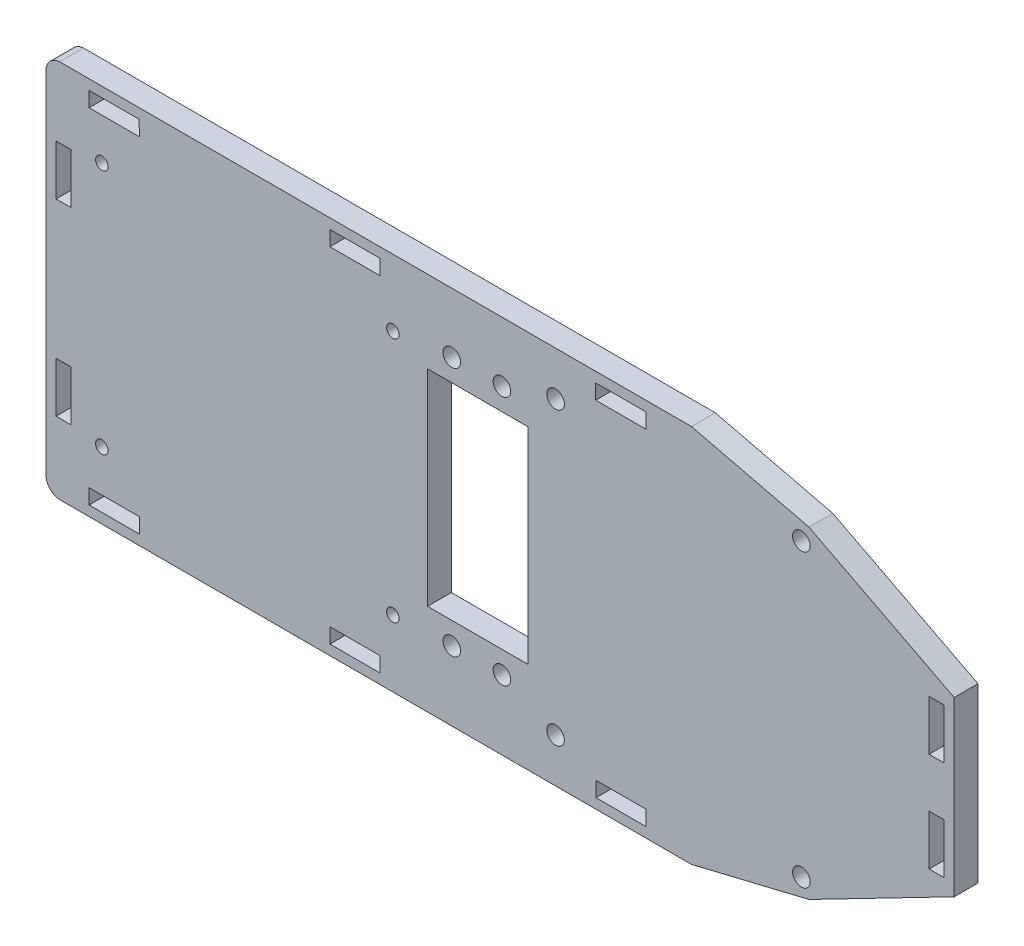
SolidWorks part; units mm, degrees
ref_plane "Front Plane" through (0, 0, 0) normal (0, 0, 1) x (1, 0, 0)
ref_plane "Top Plane" through (0, 0, 0) normal (0, 1, 0) x (1, 0, 0)
ref_plane "Right Plane" through (0, 0, 0) normal (1, 0, 0) x (0, 0, -1)
sketch "Sketch1" plane through (0, 0, 0) normal (0, 0, 1) x (1, 0, 0)
  line L1 (-90.5, -37.785) -> (90.5, -37.785)
  line L2 (-90.5, -37.785) -> (-90.5, 37.785)
  line L3 (-90.5, 37.785) -> (90.5, 37.785)
  line L4 (90.5, -37.785) -> (90.5, 37.785)
  line L5 (-90.5, -37.785) -> (90.5, 37.785) construction
  line L6 (-90.5, 37.785) -> (90.5, -37.785) construction
  point P0 (0, 0)
extrude "Boss-Extrude2" add sketch "Sketch1" along normal blind 4.75
sketch "Sketch6" plane through (0, 0, 4.75) normal (0, 0, 1) x (1, 0, 0)
  line L0 (-90.5, 0) -> (90.5, 0) construction
  line L1 (-90.5, 37.785) -> (-90.5, -37.785) construction
  line L2 (90.5, -37.785) -> (90.5, 37.785) construction
  line L3 (0, 37.785) -> (0, -37.785) construction
  line L4 (90.5, 37.785) -> (-90.5, 37.785) construction
  line L5 (-90.5, -37.785) -> (90.5, -37.785) construction
  line L6 (-90.5, 34.4318) -> (-90.5, -34.4318)
  line L7 (90.5, 17.2) -> (90.5, -17.2)
  line L10 (-21.3732, 40.787) -> (-21.3732, -34.783) construction
  line L11 (-81.9134, 32.786) -> (-71.8797, 32.7858)
  line L12 (-88.5, 23.75) -> (-85.5, 23.75)
  line L13 (-88.5, 23.75) -> (-88.5, 13.75)
  line L14 (-88.5, 13.75) -> (-85.5, 13.75)
  line L15 (-85.5, 23.75) -> (-85.5, 13.75)
  line L16 (-88.5, -13.75) -> (-85.5, -13.75)
  line L17 (-88.5, -13.75) -> (-88.5, -23.75)
  line L18 (-88.5, -23.75) -> (-85.5, -23.75)
  line L19 (-85.5, -13.75) -> (-85.5, -23.75)
  line L20 (-33.9297, 32.785) -> (-33.9309, 35.785)
  line L21 (-33.9297, 32.785) -> (-23.9273, 32.7887)
  line L22 (-33.9309, 35.785) -> (-23.931, 35.785)
  line L23 (-23.9273, 32.7887) -> (-23.931, 35.785)
  line L24 (-71.8797, 32.7858) -> (-71.9473, 35.785)
  line L25 (-81.9134, 32.786) -> (-81.9472, 35.785)
  line L26 (-81.9472, 35.785) -> (-71.9473, 35.785)
  line L27 (-81.9134, -32.785) -> (-71.8797, -32.7852)
  line L28 (-71.9135, -35.785) -> (-71.8797, -32.7852)
  line L29 (-81.9135, -35.785) -> (-71.9135, -35.785)
  line L30 (-81.9135, -35.785) -> (-81.9134, -32.785)
  line L31 (-33.9026, -35.7859) -> (-23.8868, -35.7861)
  line L32 (-33.9026, -35.7859) -> (-33.9037, -32.7859)
  line L33 (-23.8868, -35.7861) -> (-23.8868, -32.7861)
  line L34 (-33.9037, -32.7859) -> (-23.8868, -32.7861)
  line L35 (85.5, 14.9) -> (85.5, 4.9)
  line L36 (88.5, 14.9) -> (88.5, 4.9)
  line L37 (85.5, 4.9) -> (88.5, 4.9)
  line L38 (85.5, 14.9) -> (88.5, 14.9)
  line L40 (29.053, 32.7887) -> (29.053, 35.785)
  line L41 (19.053, 32.7887) -> (29.053, 32.7887)
  line L42 (19.053, 32.7887) -> (19.053, 35.785)
  line L43 (19.053, 35.785) -> (29.053, 35.785)
  line L44 (19.1132, -32.785) -> (29.053, -32.785)
  line L45 (19.1132, -35.785) -> (19.1132, -32.785)
  line L46 (19.1132, -35.785) -> (29.053, -35.785)
  line L47 (29.053, -35.785) -> (29.053, -32.785)
  line L50 (-87.3981, 37.785) -> (38.1419, 37.785)
  line L51 (-14.4594, 21.457) -> (5.5406, 21.457)
  line L52 (-14.4594, 21.457) -> (-14.4594, -19.543)
  line L53 (-14.4594, -19.543) -> (5.5406, -19.543)
  line L54 (5.5406, 21.457) -> (5.5406, -19.543)
  line L58 (-87.3981, -37.785) -> (38.1419, -37.785)
  line L60 (85.5, -14.9) -> (88.5, -14.9)
  line L61 (88.5, -14.9) -> (88.5, -4.9)
  line L62 (85.5, -4.9) -> (88.5, -4.9)
  line L63 (85.5, -14.9) -> (85.5, -4.9)
  line L64 (38.1419, -37.785) -> (61.5528, -32.1352)
  line L65 (61.5528, -32.1352) -> (90.5, -17.2)
  line L66 (38.1419, 37.785) -> (61.5528, 32.14)
  line L67 (61.5528, 32.14) -> (90.5, 17.2)
  arc A0 (-87.3981, 37.785) -> (-90.5, 34.4318) centre (-87.5923, 34.8533) ccw
  arc A1 (-90.5, -34.4318) -> (-87.3981, -37.785) centre (-87.5923, -34.8533) ccw
  circle A8 centre (-9.6294, 25.857) radius 1.75
  circle A9 centre (0.3706, 25.857) radius 1.75
  circle A10 centre (0.3706, -23.943) radius 1.75
  circle A11 centre (-9.6294, -23.943) radius 1.75
  circle A12 centre (11.053, -29) radius 1.75
  circle A13 centre (11.053, 29) radius 1.75
  circle A14 centre (60.053, -29) radius 1.75
  circle A15 centre (60.053, 29) radius 1.75
  circle A16 centre (-79.3732, 24.5) radius 1.25
  circle A17 centre (-79.3732, -24.5) radius 1.25
  circle A18 centre (-21.3732, -24.5) radius 1.25
  circle A19 centre (-21.3732, 24.5) radius 1.25
  point P18 (0, 0)
  point P21 (90.5, 0)
  point P22 (0, 0)
  line M4 (90.5, -37.785) -> (90.5, 37.785)
  line M5 (90.5, 37.785) -> (-90.5, 37.785)
  line M6 (-90.5, 37.785) -> (-90.5, -37.785)
  line M7 (-90.5, -37.785) -> (90.5, -37.785)
  dimension "D1" = 58
  dimension "D3" = 49
  dimension "D2" = 29
  dimension "D4" = 58
  dimension "D10" = 2
  dimension "D11" = 4.4
  dimension "D16" = 32.14
  dimension "D17" = 2
  dimension "D5" = 2
  dimension "D6" = 2
  dimension "D7" = 2
  dimension "D8" = 43
  dimension "D9" = 49.8
  dimension "D12" = 4.4
  dimension "D13" = 58
  dimension "D14" = 49
  dimension "D15" = 24.5
extrude "Cut-Extrude7" cut sketch "Sketch6" against normal blind 9 contours L38 L35 L37 L36 | L43 L42 L41 L40 | A9 | A8 | A11 | A10 | L46 L47 L44 L45 | L21 L23 L22 L20 | L26 L25 L11 L24 | A0 M5 M6 | L15 L12 L13 L14 | L19 L16 L17 L18 | A1 M6 M7 | L30 L29 L28 L27 | A16 | L34 L32 L31 L33 | L65 L64 M7 M4 | L66 L67 M4 M5 | L54 L51 L52 L53 | A17 | A18 | L44 L47 L46 L45 | A10 | L52 L51 L54 L53 | L60 L61 L62 L63 | A12 | A14 | A13 | A15 | A19 region at (-89.8524, 37.1595, 4.75) region at (-89.8524, -37.1595, 4.75) region at (75.0644, 31.3167, 4.75) region at (75.0611, -31.3164, 4.75) region at (-76.9218, 34.2846, 4.75) region at (-87, 18.75, 4.75) region at (-87, -18.75, 4.75) region at (-28.9307, 34.2859, 4.75) region at (-76.9051, -34.2842, 4.75) region at (-28.895, -34.286, 4.75) region at (87, 9.9, 4.75) region at (24.053, 34.2869, 4.75) region at (24.0831, -34.285, 4.75) region at (-4.4594, 0.957, 4.75) region at (-9.6294, 25.857, 4.75) region at (0.3706, 25.857, 4.75) region at (0.3706, -23.943, 4.75) region at (-9.6294, -23.943, 4.75) region at (-79.3732, 24.5, 4.75) region at (-79.3732, -24.5, 4.75) region at (-21.3732, -24.5, 4.75)
